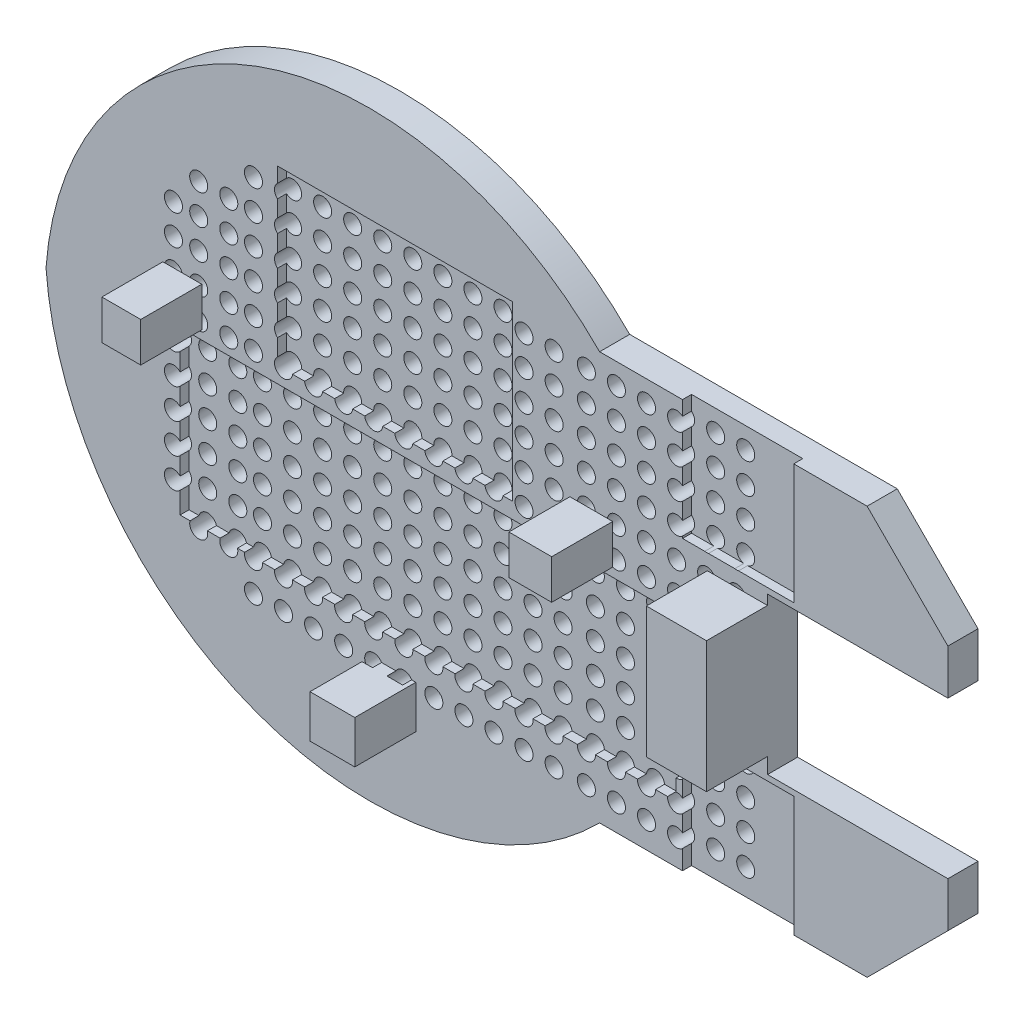
SolidWorks part; units mm, degrees
ref_plane "Front Plane" through (0, 0, 0) normal (0, 0, 1) x (1, 0, 0)
ref_plane "Top Plane" through (0, 0, 0) normal (0, 1, 0) x (1, 0, 0)
ref_plane "Right Plane" through (0, 0, 0) normal (1, 0, 0) x (0, 0, -1)
sketch "Sketch1" plane through (0, 0, 0) normal (0, 0, 1) x (1, 0, 0)
  line L1 (0, 0) -> (0, -26)
  line L2 (0, 26) -> (60, 26)
  line L3 (0, -26) -> (60, -26)
  line L4 (60, 26) -> (60, 41)
  line L5 (60, -26) -> (60, -41)
  line L6 (60, 41) -> (33.1299, 67.8701)
  line L7 (33.1299, 67.8701) -> (-55.8501, 67.8701)
  line L8 (60, -41) -> (33.1299, -67.8701)
  line L9 (33.1299, -67.8701) -> (-55.8501, -67.8701)
  line L10 (-55.8501, 67.8701) -> (-55.8501, 145.9436) construction
  line L11 (-55.8501, 145.9436) -> (-55.8501, -286.005) construction
  line L22 (0, 26) -> (0, 0)
  line L24 (-132.4482, 99.7954) -> (-270.7239, 99.7954) construction
  line L25 (-132.4482, 8.0579) -> (-132.4482, 125.9405) construction
  line L26 (-132.4482, -8.0579) -> (-132.4482, -125.1714) construction
  line L27 (-132.4482, -99.7954) -> (-270.7239, -99.7954) construction
  arc A7 (-240, 0) -> (-55.8501, 67.8701) centre (-132.4482, -8.0579) cw
  arc A8 (-55.8501, -67.8701) -> (-240, 0) centre (-132.4482, 8.0579) cw
  dimension "D11" = 199.5908
  dimension "D12" = 240
  dimension "D10" = 135.7401
  dimension "D1" = 26
  dimension "D2" = 26
  dimension "D3" = 60
  dimension "D4" = 15
  dimension "D5" = 15
  dimension "D6" = 135
  dimension "D7" = 38
  dimension "D8" = 38
  dimension "D9" = 135
  dimension "D15" = 88.98
  dimension "D16" = 88.98
extrude "Boss-Extrude1" add sketch "Sketch1" along normal blind 10 and the other way blind 0.01
sketch "Sketch3" plane through (0, 0, 10) normal (0, 0, 1) x (1, 0, 0)
  line L0 (33.1299, 67.8701) -> (-55.8501, 67.8701) construction
  line L1 (-28.273, 67.8701) -> (8.727, 67.8701)
  line L2 (-28.273, 67.8701) -> (-28.273, 27.8701)
  line L3 (-28.273, 27.8701) -> (8.727, 27.8701)
  line L4 (8.727, 67.8701) -> (8.727, 27.8701)
  dimension "D1" = 40
  dimension "D2" = 37
extrude "Cut-Extrude1" cut sketch "Sketch3" against normal blind 3 contours L2 L1 L4 L3
sketch "Sketch5" plane through (0, 0, 10) normal (0, 0, 1) x (1, 0, 0)
  line L0 (-55.8501, -67.8701) -> (33.1299, -67.8701) construction
  line L1 (-28.273, -27.8701) -> (8.727, -27.8701)
  line L2 (-28.273, -27.8701) -> (-28.273, -67.8701)
  line L3 (-28.273, -67.8701) -> (8.727, -67.8701)
  line L4 (8.727, -27.8701) -> (8.727, -67.8701)
extrude "Cut-Extrude3" cut sketch "Sketch5" against normal blind 3
sketch "Sketch7" plane through (0, 0, 10) normal (0, 0, 1) x (1, 0, 0)
  line L1 (-195.4131, 5.0562) -> (-30.4131, 5.0562)
  line L2 (-195.4131, 5.0562) -> (-195.4131, -48.9438)
  line L3 (-195.4131, -48.9438) -> (-30.4131, -48.9438)
  line L4 (-30.4131, 5.0562) -> (-30.4131, -48.9438)
  dimension "D1" = 54
  dimension "D2" = 165
extrude "Cut-Extrude4" cut sketch "Sketch7" against normal blind 3
sketch "Sketch8" plane through (0, 0, 10) normal (0, 0, 1) x (1, 0, 0)
  line L1 (-162.9927, 67.8133) -> (-84.7927, 67.8133)
  line L2 (-162.9927, 67.8133) -> (-162.9927, 10.3133)
  line L3 (-162.9927, 10.3133) -> (-84.7927, 10.3133)
  line L4 (-84.7927, 67.8133) -> (-84.7927, 10.3133)
  dimension "D1" = 78.2
  dimension "D2" = 57.5
extrude "Cut-Extrude5" cut sketch "Sketch8" against normal blind 3
sketch "Sketch9" plane through (0, 0, 10) normal (0, 0, 1) x (1, 0, 0)
  line L1 (-201.1086, 21.1542) -> (-188.1842, 21.1542)
  line L2 (-201.1086, 21.1542) -> (-201.1086, 8.0108)
  line L3 (-201.1086, 8.0108) -> (-188.1842, 8.0108)
  line L4 (-188.1842, 21.1542) -> (-188.1842, 8.0108)
  line L5 (-65.7317, 21.1542) -> (-51.493, 21.1542)
  line L6 (-65.7317, 21.1542) -> (-65.7317, 8.0108)
  line L7 (-65.7317, 8.0108) -> (-51.493, 8.0108)
  line L8 (-51.493, 21.1542) -> (-51.493, 8.0108)
  line L9 (-131.8867, -57.9252) -> (-116.9909, -57.9252)
  line L10 (-131.8867, -57.9252) -> (-131.8867, -72.1638)
  line L11 (-131.8867, -72.1638) -> (-116.9909, -72.1638)
  line L12 (-116.9909, -57.9252) -> (-116.9909, -72.1638)
extrude "Boss-Extrude2" add sketch "Sketch9" along normal blind 20.3
sketch "Sketch11" plane through (0, 0, -0.01) normal (0, 0, -1) x (-1, 0, 0)
  circle A0 centre (70.989, 60.5844) radius 3
  circle A1 centre (80.989, 60.5844) radius 3
  circle A2 centre (90.989, 60.5844) radius 3
  circle A3 centre (100.989, 60.5844) radius 3
  circle A4 centre (110.989, 60.5844) radius 3
  circle A5 centre (120.989, 60.5844) radius 3
  circle A6 centre (130.989, 60.5844) radius 3
  circle A7 centre (140.989, 60.5844) radius 3
  circle A8 centre (150.989, 60.5844) radius 3
  circle A9 centre (160.989, 60.5844) radius 3
  circle A10 centre (170.989, 60.5844) radius 3
  circle A11 centre (80.989, 50.5844) radius 3
  circle A12 centre (90.989, 50.5844) radius 3
  circle A13 centre (100.989, 50.5844) radius 3
  circle A14 centre (110.989, 50.5844) radius 3
  circle A15 centre (120.989, 50.5844) radius 3
  circle A16 centre (130.989, 50.5844) radius 3
  circle A17 centre (140.989, 50.5844) radius 3
  circle A18 centre (150.989, 50.5844) radius 3
  circle A19 centre (160.989, 50.5844) radius 3
  circle A20 centre (170.989, 50.5844) radius 3
  circle A21 centre (80.989, 40.5844) radius 3
  circle A22 centre (90.989, 40.5844) radius 3
  circle A23 centre (100.989, 40.5844) radius 3
  circle A24 centre (110.989, 40.5844) radius 3
  circle A25 centre (120.989, 40.5844) radius 3
  circle A26 centre (130.989, 40.5844) radius 3
  circle A27 centre (140.989, 40.5844) radius 3
  circle A28 centre (150.989, 40.5844) radius 3
  circle A29 centre (160.989, 40.5844) radius 3
  circle A30 centre (170.989, 40.5844) radius 3
  circle A31 centre (80.989, 30.5844) radius 3
  circle A32 centre (90.989, 30.5844) radius 3
  circle A33 centre (100.989, 30.5844) radius 3
  circle A34 centre (110.989, 30.5844) radius 3
  circle A35 centre (120.989, 30.5844) radius 3
  circle A36 centre (130.989, 30.5844) radius 3
  circle A37 centre (140.989, 30.5844) radius 3
  circle A38 centre (150.989, 30.5844) radius 3
  circle A39 centre (160.989, 30.5844) radius 3
  circle A40 centre (170.989, 30.5844) radius 3
  circle A41 centre (80.989, 20.5844) radius 3
  circle A42 centre (90.989, 20.5844) radius 3
  circle A43 centre (100.989, 20.5844) radius 3
  circle A44 centre (110.989, 20.5844) radius 3
  circle A45 centre (120.989, 20.5844) radius 3
  circle A46 centre (130.989, 20.5844) radius 3
  circle A47 centre (140.989, 20.5844) radius 3
  circle A48 centre (150.989, 20.5844) radius 3
  circle A49 centre (160.989, 20.5844) radius 3
  circle A50 centre (170.989, 20.5844) radius 3
  circle A51 centre (80.989, 10.5844) radius 3
  circle A52 centre (90.989, 10.5844) radius 3
  circle A53 centre (100.989, 10.5844) radius 3
  circle A54 centre (110.989, 10.5844) radius 3
  circle A55 centre (120.989, 10.5844) radius 3
  circle A56 centre (130.989, 10.5844) radius 3
  circle A57 centre (140.989, 10.5844) radius 3
  circle A58 centre (150.989, 10.5844) radius 3
  circle A59 centre (160.989, 10.5844) radius 3
  circle A60 centre (170.989, 10.5844) radius 3
  circle A61 centre (80.989, 0.5844) radius 3
  circle A62 centre (90.989, 0.5844) radius 3
  circle A63 centre (100.989, 0.5844) radius 3
  circle A64 centre (110.989, 0.5844) radius 3
  circle A65 centre (120.989, 0.5844) radius 3
  circle A66 centre (130.989, 0.5844) radius 3
  circle A67 centre (140.989, 0.5844) radius 3
  circle A68 centre (150.989, 0.5844) radius 3
  circle A69 centre (160.989, 0.5844) radius 3
  circle A70 centre (170.989, 0.5844) radius 3
  circle A71 centre (80.989, -9.4156) radius 3
  circle A72 centre (90.989, -9.4156) radius 3
  circle A73 centre (100.989, -9.4156) radius 3
  circle A74 centre (110.989, -9.4156) radius 3
  circle A75 centre (120.989, -9.4156) radius 3
  circle A76 centre (130.989, -9.4156) radius 3
  circle A77 centre (140.989, -9.4156) radius 3
  circle A78 centre (150.989, -9.4156) radius 3
  circle A79 centre (160.989, -9.4156) radius 3
  circle A80 centre (170.989, -9.4156) radius 3
  circle A81 centre (80.989, -19.4156) radius 3
  circle A82 centre (90.989, -19.4156) radius 3
  circle A83 centre (100.989, -19.4156) radius 3
  circle A84 centre (110.989, -19.4156) radius 3
  circle A85 centre (120.989, -19.4156) radius 3
  circle A86 centre (130.989, -19.4156) radius 3
  circle A87 centre (140.989, -19.4156) radius 3
  circle A88 centre (150.989, -19.4156) radius 3
  circle A89 centre (160.989, -19.4156) radius 3
  circle A90 centre (170.989, -19.4156) radius 3
  circle A91 centre (80.989, -29.4156) radius 3
  circle A92 centre (90.989, -29.4156) radius 3
  circle A93 centre (100.989, -29.4156) radius 3
  circle A94 centre (110.989, -29.4156) radius 3
  circle A95 centre (120.989, -29.4156) radius 3
  circle A96 centre (130.989, -29.4156) radius 3
  circle A97 centre (140.989, -29.4156) radius 3
  circle A98 centre (150.989, -29.4156) radius 3
  circle A99 centre (160.989, -29.4156) radius 3
  circle A100 centre (170.989, -29.4156) radius 3
  circle A101 centre (80.989, -39.4156) radius 3
  circle A102 centre (90.989, -39.4156) radius 3
  circle A103 centre (100.989, -39.4156) radius 3
  circle A104 centre (110.989, -39.4156) radius 3
  circle A105 centre (120.989, -39.4156) radius 3
  circle A106 centre (130.989, -39.4156) radius 3
  circle A107 centre (140.989, -39.4156) radius 3
  circle A108 centre (150.989, -39.4156) radius 3
  circle A109 centre (160.989, -39.4156) radius 3
  circle A110 centre (170.989, -39.4156) radius 3
  circle A111 centre (80.989, -49.4156) radius 3
  circle A112 centre (90.989, -49.4156) radius 3
  circle A113 centre (100.989, -49.4156) radius 3
  circle A114 centre (110.989, -49.4156) radius 3
  circle A115 centre (120.989, -49.4156) radius 3
  circle A116 centre (130.989, -49.4156) radius 3
  circle A117 centre (140.989, -49.4156) radius 3
  circle A118 centre (150.989, -49.4156) radius 3
  circle A119 centre (160.989, -49.4156) radius 3
  circle A120 centre (170.989, -49.4156) radius 3
  circle A121 centre (80.989, -59.4156) radius 3
  circle A122 centre (90.989, -59.4156) radius 3
  circle A123 centre (100.989, -59.4156) radius 3
  circle A124 centre (110.989, -59.4156) radius 3
  circle A125 centre (120.989, -59.4156) radius 3
  circle A126 centre (130.989, -59.4156) radius 3
  circle A127 centre (140.989, -59.4156) radius 3
  circle A128 centre (150.989, -59.4156) radius 3
  circle A129 centre (160.989, -59.4156) radius 3
  circle A130 centre (170.989, -59.4156) radius 3
  circle A131 centre (70.989, 50.5844) radius 3
  circle A132 centre (70.989, 40.5844) radius 3
  circle A133 centre (70.989, 30.5844) radius 3
  circle A134 centre (70.989, 20.5844) radius 3
  circle A135 centre (70.989, 10.5844) radius 3
  circle A136 centre (70.989, 0.5844) radius 3
  circle A137 centre (70.989, -9.4156) radius 3
  circle A138 centre (70.989, -19.4156) radius 3
  circle A139 centre (70.989, -29.4156) radius 3
  circle A140 centre (70.989, -39.4156) radius 3
  circle A141 centre (70.989, -49.4156) radius 3
  circle A142 centre (70.989, -59.4156) radius 3
  dimension "D1" = 11
  dimension "D2" = 13
extrude "Cut-Extrude12" cut sketch "Sketch11" against normal blind 13
sketch "Sketch12" plane through (0, 0, -0.01) normal (0, 0, -1) x (-1, 0, 0)
  circle A0 centre (179.2029, 50.2603) radius 3
  circle A1 centre (189.2029, 50.2603) radius 3
  circle A2 centre (189.2029, 40.2603) radius 3
  circle A3 centre (189.2029, 30.2603) radius 3
  circle A4 centre (189.2029, 20.2603) radius 3
  circle A5 centre (189.2029, 10.2603) radius 3
  circle A6 centre (189.2029, 0.2603) radius 3
  circle A7 centre (189.2029, -9.7397) radius 3
  circle A8 centre (189.2029, -19.7397) radius 3
  circle A9 centre (189.2029, -29.7397) radius 3
  circle A10 centre (189.2029, -39.7397) radius 3
  circle A11 centre (189.2029, -49.7397) radius 3
  circle A12 centre (179.2029, 40.2603) radius 3
  circle A13 centre (179.2029, 30.2603) radius 3
  circle A14 centre (179.2029, 20.2603) radius 3
  circle A15 centre (179.2029, 10.2603) radius 3
  circle A16 centre (179.2029, 0.2603) radius 3
  circle A17 centre (179.2029, -9.7397) radius 3
  circle A18 centre (179.2029, -19.7397) radius 3
  circle A19 centre (179.2029, -29.7397) radius 3
  circle A20 centre (179.2029, -39.7397) radius 3
  circle A21 centre (179.2029, -49.7397) radius 3
  dimension "D1" = 2
  dimension "D2" = 11
extrude "Cut-Extrude13" cut sketch "Sketch12" against normal up to surface (10.01 mm away) up to face at (-153.989, -59.4156, 10)
sketch "Sketch13" plane through (0, 0, -0.01) normal (0, 0, -1) x (-1, 0, 0)
  circle A0 centre (197.6037, 40.2121) radius 3
  circle A1 centre (197.6037, 30.2121) radius 3
  circle A2 centre (197.6037, 20.2121) radius 3
  circle A3 centre (197.6037, 10.2121) radius 3
  circle A4 centre (197.6037, 0.2121) radius 3
  circle A5 centre (197.6037, -9.7879) radius 3
  circle A6 centre (197.6037, -19.7879) radius 3
  circle A7 centre (197.6037, -29.7879) radius 3
  circle A8 centre (197.6037, -39.7879) radius 3
  dimension "D1" = 9
extrude "Cut-Extrude14" cut sketch "Sketch13" against normal up to surface (10.01 mm away) up to face at (-182.2029, 40.2603, 10)
sketch "Sketch14" plane through (0, 0, -0.01) normal (0, 0, -1) x (-1, 0, 0)
  circle A0 centre (60.2552, 60.8035) radius 3
  circle A1 centre (50.2552, 60.8035) radius 3
  circle A2 centre (40.2552, 60.8035) radius 3
  circle A3 centre (30.2552, 60.8035) radius 3
  circle A4 centre (20.2552, 60.8035) radius 3
  circle A5 centre (10.2552, 60.8035) radius 3
  circle A6 centre (50.2552, 50.8035) radius 3
  circle A7 centre (40.2552, 50.8035) radius 3
  circle A8 centre (30.2552, 50.8035) radius 3
  circle A9 centre (20.2552, 50.8035) radius 3
  circle A10 centre (10.2552, 50.8035) radius 3
  circle A11 centre (50.2552, 40.8035) radius 3
  circle A12 centre (40.2552, 40.8035) radius 3
  circle A13 centre (30.2552, 40.8035) radius 3
  circle A14 centre (20.2552, 40.8035) radius 3
  circle A15 centre (10.2552, 40.8035) radius 3
  circle A16 centre (50.2552, 30.8035) radius 3
  circle A17 centre (40.2552, 30.8035) radius 3
  circle A18 centre (30.2552, 30.8035) radius 3
  circle A19 centre (20.2552, 30.8035) radius 3
  circle A20 centre (10.2552, 30.8035) radius 3
  circle A21 centre (50.2552, 20.8035) radius 3
  circle A22 centre (40.2552, 20.8035) radius 3
  circle A23 centre (30.2552, 20.8035) radius 3
  circle A24 centre (20.2552, 20.8035) radius 3
  circle A25 centre (10.2552, 20.8035) radius 3
  circle A26 centre (50.2552, 10.8035) radius 3
  circle A27 centre (40.2552, 10.8035) radius 3
  circle A28 centre (30.2552, 10.8035) radius 3
  circle A29 centre (20.2552, 10.8035) radius 3
  circle A30 centre (10.2552, 10.8035) radius 3
  circle A31 centre (50.2552, 0.8035) radius 3
  circle A32 centre (40.2552, 0.8035) radius 3
  circle A33 centre (30.2552, 0.8035) radius 3
  circle A34 centre (20.2552, 0.8035) radius 3
  circle A35 centre (10.2552, 0.8035) radius 3
  circle A36 centre (50.2552, -9.1965) radius 3
  circle A37 centre (40.2552, -9.1965) radius 3
  circle A38 centre (30.2552, -9.1965) radius 3
  circle A39 centre (20.2552, -9.1965) radius 3
  circle A40 centre (10.2552, -9.1965) radius 3
  circle A41 centre (50.2552, -19.1965) radius 3
  circle A42 centre (40.2552, -19.1965) radius 3
  circle A43 centre (30.2552, -19.1965) radius 3
  circle A44 centre (20.2552, -19.1965) radius 3
  circle A45 centre (10.2552, -19.1965) radius 3
  circle A46 centre (50.2552, -29.1965) radius 3
  circle A47 centre (40.2552, -29.1965) radius 3
  circle A48 centre (30.2552, -29.1965) radius 3
  circle A49 centre (20.2552, -29.1965) radius 3
  circle A50 centre (10.2552, -29.1965) radius 3
  circle A51 centre (50.2552, -39.1965) radius 3
  circle A52 centre (40.2552, -39.1965) radius 3
  circle A53 centre (30.2552, -39.1965) radius 3
  circle A54 centre (20.2552, -39.1965) radius 3
  circle A55 centre (10.2552, -39.1965) radius 3
  circle A56 centre (50.2552, -49.1965) radius 3
  circle A57 centre (40.2552, -49.1965) radius 3
  circle A58 centre (30.2552, -49.1965) radius 3
  circle A59 centre (20.2552, -49.1965) radius 3
  circle A60 centre (10.2552, -49.1965) radius 3
  circle A61 centre (50.2552, -59.1965) radius 3
  circle A62 centre (40.2552, -59.1965) radius 3
  circle A63 centre (30.2552, -59.1965) radius 3
  circle A64 centre (20.2552, -59.1965) radius 3
  circle A65 centre (10.2552, -59.1965) radius 3
  circle A66 centre (60.2552, 50.8035) radius 3
  circle A67 centre (60.2552, 40.8035) radius 3
  circle A68 centre (60.2552, 30.8035) radius 3
  circle A69 centre (60.2552, 20.8035) radius 3
  circle A70 centre (60.2552, 10.8035) radius 3
  circle A71 centre (60.2552, 0.8035) radius 3
  circle A72 centre (60.2552, -9.1965) radius 3
  circle A73 centre (60.2552, -19.1965) radius 3
  circle A74 centre (60.2552, -29.1965) radius 3
  circle A75 centre (60.2552, -39.1965) radius 3
  circle A76 centre (60.2552, -49.1965) radius 3
  circle A77 centre (60.2552, -59.1965) radius 3
  dimension "D1" = 6
  dimension "D2" = 13
extrude "Cut-Extrude16" cut sketch "Sketch14" against normal up to surface (10.01 mm away) up to face at (-200.6037, 40.2121, 10)
sketch "Sketch15" plane through (0, 0, 10) normal (0, 0, 1) x (1, 0, 0)
  line L0 (0, -26) -> (0, 26) construction
  line L1 (-20, 22.7016) -> (0, 22.7016)
  line L2 (-20, 22.7016) -> (-20, -20.7984)
  line L3 (-20, -20.7984) -> (0, -20.7984)
  line L4 (0, 22.7016) -> (0, -20.7984)
  dimension "D1" = 43.5
  dimension "D2" = 20
extrude "Boss-Extrude3" add sketch "Sketch15" along normal blind 20.3
sketch "Sketch4" plane through (0, 0, 7) normal (0, 0, 1) x (1, 0, 0)
  line L1 (-28.3661, -27.8728) -> (8.6339, -27.8728)
  line L2 (-28.3661, -27.8728) -> (-28.3661, -67.8728)
  line L3 (-28.3661, -67.8728) -> (8.6339, -67.8728)
  line L4 (8.6339, -27.8728) -> (8.6339, -67.8728)
  dimension "D1" = 40
  dimension "D2" = 37
